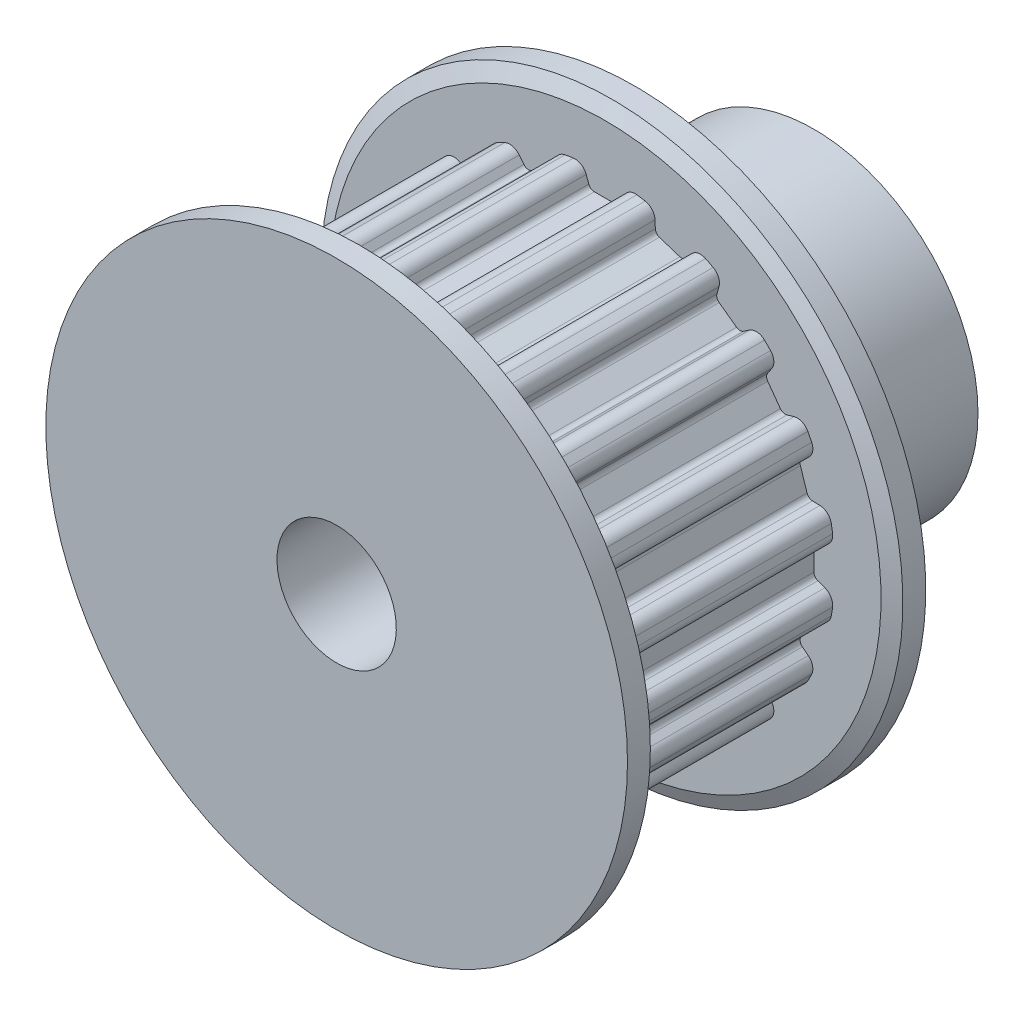
SolidWorks part; units mm, degrees
ref_plane "Front" through (0, 0, 0) normal (0, 0, 1) x (1, 0, 0)
ref_plane "Top" through (0, 0, 0) normal (0, 1, 0) x (1, 0, 0)
ref_plane "Right" through (0, 0, 0) normal (1, 0, 0) x (0, 0, -1)
sketch "support-front-body" plane through (0, 0, 0) normal (0, 0, 1) x (1, 0, 0)
  line L0 (0, 0) -> (0, 7.7) construction
  line L1 (0, 0) -> (0, -7.7) construction
  line L2 (0, 0) -> (7.7, 0) construction
  line L3 (0, 0) -> (-7.7, 0) construction
  circle A0 centre (0, 0) radius 7.7
  dimension "diam-outer" = 15.4
sketch "support-right-body" plane through (0, 0, 0) normal (1, 0, 0) x (0, 0, -1)
  line L0 (0, 0) -> (10, 0) construction
  line L1 (0, 7.7) -> (10, 7.7)
  line L2 (0, 7.7) -> (0, -7.7)
  line L3 (0, -7.7) -> (10, -7.7)
  line L4 (10, 7.7) -> (10, -7.7)
  dimension "length" = 10
sketch "support-right-chamfer" plane through (0, 0, 0) normal (1, 0, 0) x (0, 0, -1)
  line L0 (0, 0) -> (10, 0) construction
  line L1 (0, -7.7) -> (0, -6.7)
  line L2 (0, 7.7) -> (0, -7.7) construction
  line L4 (0, -6.7) -> (1, -7.7)
  line L5 (0, -7.7) -> (10, -7.7) construction
  line L7 (1, -7.7) -> (0, -7.7)
  line L9 (10, -7.7) -> (9, -7.7)
  line L11 (9, -7.7) -> (10, -6.7)
  line L12 (10, 7.7) -> (10, -7.7) construction
  line L14 (10, -6.7) -> (10, -7.7)
  dimension "height-chamfer-front" = 1
  dimension "angle-chamfer-front" = 45
  dimension "angle-chamfer-back" = 45
  dimension "height-chamfer-back" = 1
sketch "support-right-hub" plane through (0, 0, 0) normal (1, 0, 0) x (0, 0, -1)
  line L0 (16, 0) -> (10, 0) construction
  line L1 (10, 5.5) -> (16, 5.5)
  line L2 (10, 5.5) -> (10, -5.5)
  line L3 (10, -5.5) -> (16, -5.5)
  line L4 (16, 5.5) -> (16, -5.5)
  line L6 (0, 0) -> (10, 0) construction
  line L8 (0, 7.7) -> (0, -7.7) construction
  dimension "diam-hub" = 11
  dimension "length-hub" = 6
  dimension "dist-hub" = 10
sketch "support-right-bore" plane through (0, 0, 0) normal (1, 0, 0) x (0, 0, -1)
  line L0 (0, 7.7) -> (0, -7.7) construction
  line L1 (0, 2) -> (16, 2)
  line L2 (0, 2) -> (0, -2)
  line L3 (0, -2) -> (16, -2)
  line L4 (16, 2) -> (16, 0)
  line L5 (16, 0) -> (0, 0) construction
  line L6 (0, 0) -> (10, 0) construction
  line L7 (16, 0) -> (16, -2)
  line L8 (16, -2) -> (16, 2) construction
  dimension "diam-bore" = 4
  dimension "length-bore" = 16
  dimension "angle-bore-bottom" = 180
  dimension "angle-bore" = 90
sketch "support-stop-screw-hole" plane through (0, 0, 0) normal (1, 0, 0) x (0, 0, -1)
  line L1 (6.5667, 11) -> (9.4333, 11)
  line L2 (6.5667, 11) -> (6.5667, -1)
  line L3 (8, -1) -> (9.4333, -1)
  line L4 (9.4333, 11) -> (9.4333, -1)
  line L5 (8, -1) -> (8, 11) construction
  line L6 (8, -1) -> (6.5667, -1)
  line L7 (0, 0) -> (8, 0) construction
  line L8 (0, 7.7) -> (0, -7.7) construction
  dimension "diam-stop-screw-hole" = 2.8665
  dimension "dist-stop-screw-hole" = 8
  dimension "depth-stop-screw-hole" = 12
  dimension "angle-stop-screw-hole" = 180
  dimension "height-stop-screw-hole" = 11
sketch "support-front-keygroove" plane through (0, 0, 0) normal (0, 0, 1) x (1, 0, 0)
  line L0 (0, 0) -> (0, -2) construction
  line L1 (-1, 6) -> (1, 6)
  line L2 (-1, 6) -> (-1, 3.8)
  line L3 (-1, 3.8) -> (1, 3.8)
  line L4 (1, 6) -> (1, 3.8)
  line L5 (0, 0) -> (0, 2) construction
  circle A0 centre (0, 0) radius 2 construction
  dimension "width-keygroove" = 2
  dimension "dist-keygroove" = 8
  dimension "height-keygroove" = 2.2
sketch "support-front-tooth" plane through (0, 0, 0) normal (0, 0, 1) x (1, 0, 0)
  line L0 (0.5479, 7.1316) -> (0.6335, 7.3667)
  line L1 (0, 0) -> (0, 7.7) construction
  line L2 (-0.5479, 7.1316) -> (-0.6335, 7.3667)
  line L3 (-0.36, 7) -> (0.36, 7)
  line L4 (0, 7) -> (-1.0646, 7.626) construction
  line L5 (0, 7) -> (-0.5479, 7.1316) construction
  line L6 (0, 7.7) -> (0.5704, 7.6062) construction
  line L7 (0, 7.7) -> (2.4668, 7.2942) construction
  line L8 (0, 7.626) -> (0, 7) construction
  line L9 (1.0646, 7.626) -> (-1.0646, 7.626) construction
  line L10 (0, 7.626) -> (0, 8.2521) construction
  line L11 (0, 0) -> (1.2334, 7.4971) construction
  line L12 (1.4346, 7.5652) -> (1.6352, 8.1582)
  line L13 (1.6352, 8.1582) -> (3.6522, 7.4761)
  line L14 (3.6522, 7.4761) -> (3.4517, 6.883)
  line L15 (2.5836, 6.5157) -> (2.9601, 6.7755)
  line L16 (2.5836, 6.5157) -> (1.9016, 6.7464)
  line L17 (1.0646, 7.626) -> (1.0646, 8.2521)
  line L21 (-1.0646, 8.2521) -> (-1.0646, 7.626)
  line L22 (1.0646, 8.2521) -> (-1.0646, 8.2521)
  line L23 (1.9016, 6.7464) -> (1.76, 7.1814)
  line L24 (1.4346, 7.5652) -> (1.0646, 7.626) construction
  line L25 (-0.5479, 7.1316) -> (-0.5, 7) construction
  line L26 (-0.5, 7) -> (0.5, 7) construction
  line L27 (0.5, 7) -> (0.5479, 7.1316) construction
  line L28 (0.5704, 7.6062) -> (1.0093, 7.2299) construction
  arc A0 (-0.5479, 7.1316) -> (-0.36, 7) centre (-0.36, 7.2) ccw
  circle A1 centre (0, 0) radius 7.7 construction
  arc A2 (0.6335, 7.3667) -> (1.0646, 7.626) centre (1.0093, 7.2299) cw
  arc A3 (-0.6335, 7.3667) -> (-1.0646, 7.626) centre (-1.0093, 7.2299) ccw
  arc A4 (0.5479, 7.1316) -> (0.36, 7) centre (0.36, 7.2) cw
  circle A5 centre (0, 0) radius 7.7 construction
  arc A6 (1.76, 7.1814) -> (1.4346, 7.5652) centre (1.3601, 7.1722) ccw
  arc A7 (2.9601, 6.7755) -> (3.4517, 6.883) centre (3.2724, 6.5255) cw
  dimension "D3" = 0.4
  dimension "D2" = 40
  dimension "D1" = 0.2
  dimension "D4" = 1
  dimension "height-tooth" = 0.7
  dimension "pitch" = 2.5
sketch "support-right-flange" plane through (0, 0, 0) normal (1, 0, 0) x (0, 0, -1)
  line L0 (0, 4.85) -> (0, 8.1167)
  line L1 (10, 7.7) -> (10, -7.7) construction
  line L2 (0, 8.1167) -> (1, 8.1167) construction
  line L3 (1, 8.1167) -> (1, 9.75)
  line L4 (0, 9.75) -> (1, 9.75)
  line L5 (1, 8.1167) -> (1, 4.85)
  line L6 (1, 4.85) -> (0, 4.85)
  line L7 (5, 7.7) -> (5, 0) construction
  line L8 (0, 7.7) -> (10, 7.7) construction
  line L9 (0, 8.1167) -> (0, 9.75)
  line L10 (9, 4.85) -> (10, 4.85)
  line L11 (9, 8.1167) -> (9, 4.85)
  line L12 (10, 9.75) -> (9, 9.75)
  line L13 (9, 8.1167) -> (9, 9.75)
  line L14 (10, 8.1167) -> (10, 9.75)
  line L15 (10, 4.85) -> (10, 8.1167)
  line L16 (10, 0) -> (0, 0) construction
  line L17 (10, -4.85) -> (10, -8.1167)
  line L18 (10, -8.1167) -> (10, -9.75)
  line L19 (9, -8.1167) -> (9, -9.75)
  line L20 (10, -9.75) -> (9, -9.75)
  line L21 (9, -8.1167) -> (9, -4.85)
  line L22 (9, -4.85) -> (10, -4.85)
  line L23 (1, -4.85) -> (0, -4.85)
  line L24 (1, -8.1167) -> (1, -4.85)
  line L25 (0, -9.75) -> (1, -9.75)
  line L26 (1, -8.1167) -> (1, -9.75)
  line L27 (0, -8.1167) -> (0, -9.75)
  line L28 (0, -4.85) -> (0, -8.1167)
  line L29 (0, 0) -> (10, 0) construction
  line L30 (0, 8.1167) -> (1, 8.1167) construction
  line L31 (0.5, 4.85) -> (0.5, 6.4833) construction
  line L32 (0.5, 6.4833) -> (0.5, 8.1167) construction
  line L33 (0.5, 9.75) -> (0.5, 8.1167) construction
  line L34 (0, 7.7) -> (10, 7.7) construction
  dimension "angle-flange" = 180
  dimension "thickness-flange" = 1
  dimension "diam-flange-inner" = 9.7
  dimension "diam-flange-outer" = 19.5
  dimension "width-flange-inner" = 8
sketch "support-right-flange-profile" plane through (0, 0, 0) normal (1, 0, 0) x (0, 0, -1)
  line L0 (0.7668, 9.75) -> (1, 9.75)
  line L2 (1, 9.75) -> (1, 9.25)
  line L3 (1, 8.1167) -> (1, 4.85) construction
  line L4 (1, 9.25) -> (0.7668, 9.75)
  line L5 (0, 0) -> (10, 0) construction
  line L6 (5, 0) -> (5, 7.7) construction
  line L7 (9, 9.25) -> (9.2332, 9.75)
  line L8 (9, 9.75) -> (9, 9.25)
  line L9 (9.2332, 9.75) -> (9, 9.75)
  dimension "D1" = 25
  dimension "D2" = 0.5
ref_axis "ref-axis-center" through (0, 0, -10) along (0, 0, 1)
ref_plane "ref-plane-front" through (0, 0, 0) normal (0, 0, 1) x (1, 0, 0)
ref_plane "ref-plane-back" through (0, 0, -10) normal (0, 0, 1) x (1, 0, 0)
ref_plane "ref-plane-hub-front" through (0, 0, -10) normal (0, 0, 1) x (1, 0, 0)
ref_plane "ref-plane-hub-back" through (0, 0, -16) normal (0, 0, 1) x (1, 0, 0)
ref_plane "ref-plane-bore-front" through (0, 0, 0) normal (0, 0, 1) x (1, 0, 0)
ref_plane "ref-plane-bore-back" through (0, 0, -16) normal (0, 0, 1) x (1, 0, 0)
ref_plane "ref-plane-stop-screw-hole-top" through (0, 11, 0) normal (0, 1, 0) x (-1, 0, 0)
ref_axis "ref-axis-stop-screw-hole" through (0, 11, -8) along (0, -1, 0)
sketch "Sketch5" plane through (0, 0, 0) normal (1, 0, 0) x (0, 0, -1)
  line L0 (10, 7.7) -> (10, -7.7) construction
  line L1 (0, 7.7) -> (10, 7.7) construction
  line L2 (0, 7.7) -> (0, -7.7) construction
  line L3 (0, 0) -> (10, 0) construction
  line L4 (10, 7.7) -> (10, 0)
  line L5 (0, 7.7) -> (10, 7.7)
  line L6 (0, 7.7) -> (0, 0)
  line L7 (0, 0) -> (10, 0) construction
  line L8 (0, 0) -> (10, 0)
  dimension "D1" = 10
  dimension "D2" = 7.7
revolve "body" add sketch "Sketch5" angle 360 about L7
sketch "Sketch11" plane through (0, 0, 0) normal (1, 0, 0) x (0, 0, -1)
  line L0 (0, -7.7) -> (0, -6.7) construction
  line L3 (1, -7.7) -> (0, -7.7) construction
  line L5 (0, -6.7) -> (1, -7.7) construction
  line L8 (0, -7.7) -> (0, -6.7)
  line L9 (1, -7.7) -> (0, -7.7)
  line L10 (0, -6.7) -> (1, -7.7)
  line L11 (0, 0) -> (10, 0) construction
  line L12 (0, 0) -> (10, 0) construction
revolve "cut-chamfer-front" [suppressed] cut sketch "Sketch11" angle 360 about L12
sketch "Sketch13" plane through (0, 0, 0) normal (1, 0, 0) x (0, 0, -1)
  line L0 (0, 0) -> (10, 0) construction
  line L1 (10, -7.7) -> (9, -7.7) construction
  line L2 (10, -6.7) -> (10, -7.7) construction
  line L3 (9, -7.7) -> (10, -6.7) construction
  line L4 (0, 0) -> (10, 0) construction
  line L5 (10, -7.7) -> (9, -7.7)
  line L6 (10, -6.7) -> (10, -7.7)
  line L7 (9, -7.7) -> (10, -6.7)
revolve "cut-chamfer-back" [suppressed] cut sketch "Sketch13" angle 360 about L4
sketch "Sketch16" plane through (0, 0, 0) normal (1, 0, 0) x (0, 0, -1)
  line L0 (16, 5.5) -> (16, -5.5) construction
  line L1 (10, 5.5) -> (16, 5.5) construction
  line L2 (16, 0) -> (10, 0) construction
  line L3 (10, 5.5) -> (10, -5.5) construction
  line L4 (16, 5.5) -> (16, 0)
  line L5 (10, 5.5) -> (16, 5.5)
  line L6 (16, 0) -> (10, 0) construction
  line L7 (10, 5.5) -> (10, 0)
  line L8 (16, 0) -> (10, 0)
revolve "body-hub" add sketch "Sketch16" angle 360 about L6
sketch "Sketch17" plane through (0, 0, 0) normal (1, 0, 0) x (0, 0, -1)
  line L0 (16, 2) -> (16, 0) construction
  line L1 (16, 0) -> (0, 0) construction
  line L2 (0, 2) -> (16, 2) construction
  line L3 (0, 2) -> (0, -2) construction
  line L4 (16, 2) -> (16, 0)
  line L5 (16, 0) -> (0, 0) construction
  line L6 (0, 2) -> (16, 2)
  line L7 (0, 2) -> (0, 0)
  line L8 (16, 0) -> (0, 0)
  dimension "D1" = 2
revolve "body-bore" cut sketch "Sketch17" angle 360 about L5
sketch "Sketch19" plane through (0, 0, 0) normal (1, 0, 0) x (0, 0, -1)
  line L0 (6.5667, 11) -> (9.4333, 11) construction
  line L1 (8, -1) -> (8, 11) construction
  line L2 (9.4333, 11) -> (9.4333, -1) construction
  line L3 (8, -1) -> (9.4333, -1) construction
  line L4 (8, 11) -> (9.4333, 11)
  line L5 (8, -1) -> (8, 11) construction
  line L6 (9.4333, 11) -> (9.4333, -1)
  line L7 (8, -1) -> (9.4333, -1)
  line L8 (8, -1) -> (8, 11)
revolve "body-stop-screw-hole" [suppressed] cut sketch "Sketch19" angle 360 about L5
pattern_circular "pattern-stop-screw-hole" [suppressed] count 2 every 90 about axis through (0, 0, -10) along (0, 0, 1) reverse direction yes
sketch "Sketch21" plane through (0, 0, 0) normal (0, 0, 1) x (1, 0, 0)
  line L0 (-1, 6) -> (1, 6) construction
  line L1 (-1, 6) -> (-1, 3.8) construction
  line L2 (-1, 3.8) -> (1, 3.8) construction
  line L3 (1, 6) -> (1, 3.8) construction
  line L4 (-1, 6) -> (1, 6)
  line L5 (-1, 6) -> (-1, 3.8)
  line L6 (-1, 3.8) -> (1, 3.8)
  line L7 (1, 6) -> (1, 3.8)
extrude "cut-keygroove" [suppressed] cut sketch "Sketch21" against normal up to surface (17.5 mm away) up to plane "ref-plane-bore-back"
sketch "Sketch23" plane through (0, 0, 0) normal (0, 0, 1) x (1, 0, 0)
  line L0 (0.5479, 7.1316) -> (0.6335, 7.3667) construction
  line L1 (-0.5479, 7.1316) -> (-0.6335, 7.3667) construction
  line L2 (-1.0646, 8.2521) -> (-1.0646, 7.626) construction
  line L3 (1.0646, 8.2521) -> (-1.0646, 8.2521) construction
  line L4 (1.0646, 7.626) -> (1.0646, 8.2521) construction
  line L6 (0.5479, 7.1316) -> (0.6335, 7.3667)
  line L7 (-0.5479, 7.1316) -> (-0.6335, 7.3667)
  line L8 (-1.0646, 8.2521) -> (-1.0646, 7.626)
  line L9 (1.0646, 8.2521) -> (-1.0646, 8.2521)
  line L10 (1.0646, 7.626) -> (1.0646, 8.2521)
  line L11 (-0.36, 7) -> (0.36, 7) construction
  line L12 (-0.36, 7) -> (0.36, 7)
  arc A0 (0.36, 7) -> (0.5479, 7.1316) centre (0.36, 7.2) ccw construction
  arc A1 (-0.5479, 7.1316) -> (-0.36, 7) centre (-0.36, 7.2) ccw construction
  arc A2 (-0.6335, 7.3667) -> (-1.0646, 7.626) centre (-1.0093, 7.2299) ccw construction
  arc A3 (1.0646, 7.626) -> (0.6335, 7.3667) centre (1.0093, 7.2299) ccw construction
  arc A4 (0.36, 7) -> (0.5479, 7.1316) centre (0.36, 7.2) ccw
  arc A5 (-0.5479, 7.1316) -> (-0.36, 7) centre (-0.36, 7.2) ccw
  arc A6 (-0.6335, 7.3667) -> (-1.0646, 7.626) centre (-1.0093, 7.2299) ccw
  arc A7 (1.0646, 7.626) -> (0.6335, 7.3667) centre (1.0093, 7.2299) ccw
extrude "cut-tooth" cut sketch "Sketch23" against normal up to surface (10 mm away) up to plane "ref-plane-back"
pattern_circular "pattern-tooth" count 20 over 360 about axis through (0, 0, -10) along (0, 0, 1) of "cut-tooth"
sketch "Sketch25" plane through (0, 0, 0) normal (1, 0, 0) x (0, 0, -1)
  line L0 (0, 0) -> (10, 0) construction
  line L1 (1, 4.85) -> (0, 4.85) construction
  line L2 (1, 8.1167) -> (1, 4.85) construction
  line L4 (0, 9.75) -> (1, 9.75) construction
  line L5 (0, 8.1167) -> (0, 9.75) construction
  line L6 (0, 4.85) -> (0, 8.1167) construction
  line L7 (0, 0) -> (10, 0) construction
  line L8 (1, 4.85) -> (0, 4.85)
  line L9 (1, 8.1167) -> (1, 4.85)
  line L10 (0, 9.75) -> (1, 9.75)
  line L11 (1, 8.1167) -> (1, 9.75) construction
  line L12 (0, 8.1167) -> (0, 9.75)
  line L13 (0, 4.85) -> (0, 8.1167)
  line L14 (1, 8.1167) -> (1, 9.75)
revolve "body-flange-front" add sketch "Sketch25" angle 360 about L7
sketch "Sketch26" plane through (0, 0, 0) normal (1, 0, 0) x (0, 0, -1)
  line L0 (10, 0) -> (0, 0) construction
  line L1 (9, 4.85) -> (10, 4.85) construction
  line L2 (9, 8.1167) -> (9, 4.85) construction
  line L4 (10, 9.75) -> (9, 9.75) construction
  line L5 (10, 8.1167) -> (10, 9.75) construction
  line L6 (10, 4.85) -> (10, 8.1167) construction
  line L7 (10, 0) -> (0, 0) construction
  line L8 (9, 4.85) -> (10, 4.85)
  line L9 (9, 8.1167) -> (9, 4.85)
  line L10 (10, 9.75) -> (9, 9.75)
  line L11 (9, 8.1167) -> (9, 9.75) construction
  line L12 (10, 8.1167) -> (10, 9.75)
  line L13 (10, 4.85) -> (10, 8.1167)
  line L14 (9, 8.1167) -> (9, 9.75)
revolve "body-flange-back" add sketch "Sketch26" angle 360 about L7
sketch "Sketch28" plane through (0, 0, 0) normal (1, 0, 0) x (0, 0, -1)
  line L0 (1, 9.75) -> (1, 9.25) construction
  line L1 (0.7668, 9.75) -> (1, 9.75) construction
  line L2 (1, 9.25) -> (0.7668, 9.75) construction
  line L3 (1, 9.75) -> (1, 9.25)
  line L4 (0.7668, 9.75) -> (1, 9.75)
  line L5 (1, 9.25) -> (0.7668, 9.75)
  line L6 (10, 0) -> (0, 0) construction
  line L7 (10, 0) -> (0, 0) construction
revolve "body-flange-profile-front" cut sketch "Sketch28" angle 360 about L7
sketch "Sketch29" plane through (0, 0, 0) normal (1, 0, 0) x (0, 0, -1)
  line L0 (10, 0) -> (0, 0) construction
  line L1 (9, 9.75) -> (9, 9.25) construction
  line L2 (9.2332, 9.75) -> (9, 9.75) construction
  line L3 (9, 9.25) -> (9.2332, 9.75) construction
  line L4 (10, 0) -> (0, 0) construction
  line L5 (9, 9.75) -> (9, 9.25)
  line L6 (9.2332, 9.75) -> (9, 9.75)
  line L7 (9, 9.25) -> (9.2332, 9.75)
revolve "body-flange-profile-back" cut sketch "Sketch29" angle 360 about L4
sketch "support-right-cut-body" plane through (0, 0, 0) normal (1, 0, 0) x (0, 0, -1)
  line L0 (10, 7.7) -> (10, -7.7) construction
  line L1 (0, 7.7) -> (10, 7.7) construction
  line L2 (0, 7.7) -> (0, -7.7) construction
  line L3 (0, -7.7) -> (10, -7.7) construction
  line L4 (10, 7.7) -> (10, -7.7) construction
  line L5 (0, 7.7) -> (0, -7.7) construction
  line L6 (0, 7.7) -> (10, 7.7) construction
  line L7 (0, -7.7) -> (10, -7.7) construction
  line L8 (10, 0) -> (0, 0) construction
  line L9 (5, 7.7) -> (5, -7.7) construction
  line L10 (10, 58.5) -> (6.6667, 58.5)
  line L11 (10, 58.5) -> (10, -58.5)
  line L12 (10, -58.5) -> (6.6667, -58.5)
  line L13 (6.6667, 58.5) -> (6.6667, -58.5)
  line L14 (0, 58.5) -> (3.3333, 58.5)
  line L15 (0, 58.5) -> (0, -58.5)
  line L16 (0, -58.5) -> (3.3333, -58.5)
  line L17 (3.3333, 58.5) -> (3.3333, -58.5)
  line L18 (6.6667, 58.5) -> (3.3333, 58.5) construction
  line L19 (3.3333, -58.5) -> (5, -58.5) construction
  line L21 (10, 5.5) -> (6.6667, 5.5)
  line L23 (10, 5.5) -> (16, 5.5) construction
  line L24 (10, -5.5) -> (6.6667, -5.5)
  line L25 (0, 5.5) -> (3.3333, 5.5)
  line L26 (0, -5.5) -> (3.3333, -5.5)
  dimension "diam" = 117
sketch "support-front-cut-body" plane through (0, 0, 0) normal (0, 0, 1) x (1, 0, 0)
  line L0 (58.5, 0) -> (-58.5, 0) construction
  line L1 (0, 58.5) -> (0, 5.5) construction
  line L2 (0, 7.7) -> (0, -7.7) construction
  line L4 (0, 58.5) -> (-54.972, -20.0082) construction
  line L6 (0, -5.5) -> (0, -58.5) construction
  circle A0 centre (0, 32) radius 15.1998
  circle A1 centre (0, 0) radius 58.5 construction
  circle A2 centre (0, 0) radius 5.5 construction
  dimension "D1" = 35
sketch "Sketch31" plane through (0, 0, 0) normal (1, 0, 0) x (0, 0, -1)
  line L0 (0, 58.5) -> (0, -58.5) construction
  line L1 (0, 58.5) -> (3.3333, 58.5) construction
  line L2 (3.3333, 58.5) -> (3.3333, -58.5) construction
  line L3 (10, 58.5) -> (10, -58.5) construction
  line L4 (10, 58.5) -> (6.6667, 58.5) construction
  line L5 (6.6667, 58.5) -> (6.6667, -58.5) construction
  line L7 (0, 58.5) -> (0, 5.5)
  line L8 (0, 58.5) -> (3.3333, 58.5)
  line L9 (3.3333, 58.5) -> (3.3333, 5.5)
  line L10 (10, 58.5) -> (10, 5.5)
  line L11 (10, 58.5) -> (6.6667, 58.5)
  line L12 (6.6667, 58.5) -> (6.6667, 5.5)
  line L13 (10, 5.5) -> (6.6667, 5.5)
  line L14 (10, 5.5) -> (6.6667, 5.5) construction
  line L15 (3.3333, 5.5) -> (0, 5.5)
  line L16 (0, 0) -> (10, 0) construction
  line L17 (10, 0) -> (0, 0) construction
revolve "cut-body" [suppressed] cut sketch "Sketch31" angle 360 about L16
sketch "Sketch33" plane through (0, 0, 0) normal (0, 0, 1) x (1, 0, 0)
  circle A0 centre (0, 32) radius 15.1998 construction
  circle A1 centre (0, 32) radius 15.1998
extrude "cut-front-body" [suppressed] cut sketch "Sketch33" against normal through all
pattern_circular "pattern-cut-front-body" [suppressed] count 6 over 360 about axis through (0, 0, -10) along (0, 0, 1)
